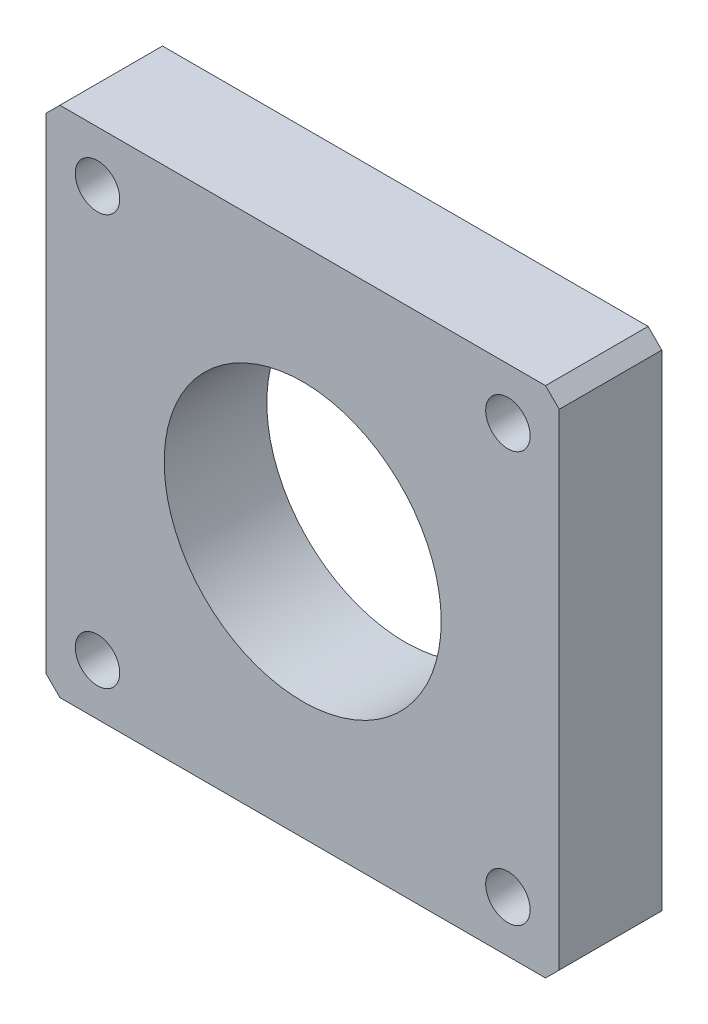
SolidWorks part; units mm, degrees
ref_plane "前视基准面" through (0, 0, 0) normal (0, 0, 1) x (1, 0, 0)
ref_plane "上视基准面" through (0, 0, 0) normal (0, 1, 0) x (1, 0, 0)
ref_plane "右视基准面" through (0, 0, 0) normal (1, 0, 0) x (0, 0, -1)
other "Configuration Table"
sketch "草图1" plane through (0, 0, 0) normal (0, 0, 1) x (1, 0, 0)
  line L1 (0, 0) -> (75, 0)
  line L2 (0, 0) -> (0, -75)
  line L3 (0, -75) -> (75, -75)
  line L4 (75, 0) -> (75, -75)
  dimension "D1" = 75
  dimension "D2" = 75
extrude "凸台-拉伸1" add sketch "草图1" along normal blind 15
chamfer "倒角1" distance 2 angle 45 4 edges at (75, -75, 7.5) (75, 0, 7.5) (0, -75, 7.5) (0, 0, 7.5)
sketch "草图2" plane through (0, 0, 15) normal (0, 0, 1) x (1, 0, 0)
  line L0 (0, -37.5) -> (75, -37.5) construction
  line L1 (0, -2) -> (0, -73) construction
  line L2 (75, -73) -> (75, -2) construction
  line L3 (37.5, 0) -> (37.5, -75) construction
  line L4 (73, 0) -> (2, 0) construction
  line L5 (2, -75) -> (73, -75) construction
  circle A0 centre (37.5, -37.5) radius 20.25
  circle A1 centre (7.5, -7.5) radius 3.25
  circle A2 centre (67.5, -7.5) radius 3.25
  circle A3 centre (67.5, -67.5) radius 3.25
  circle A4 centre (7.5, -67.5) radius 3.25
  dimension "D1" = 40.5
  dimension "D2" = 6.5
  dimension "D3" = 7.5
  dimension "D4" = 7.5
extrude "切除-拉伸1" cut sketch "草图2" against normal through all
